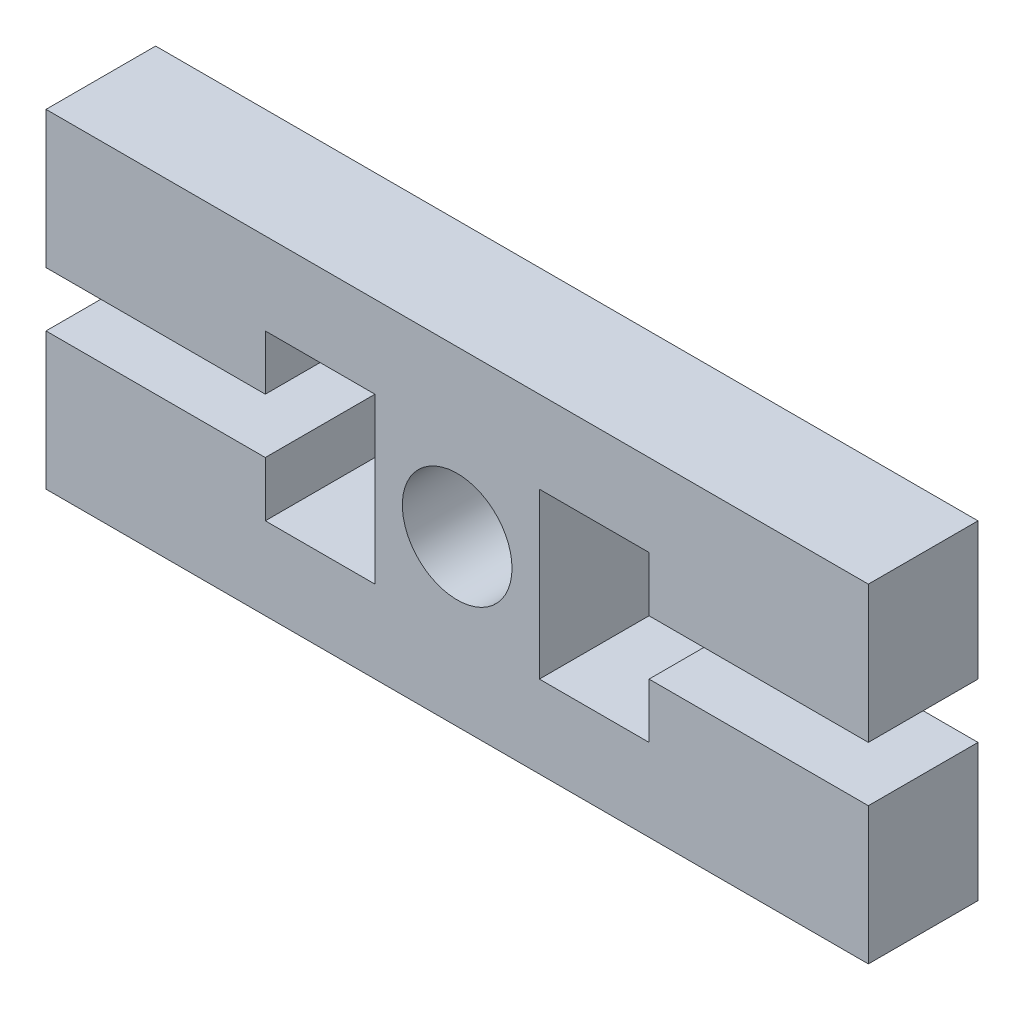
SolidWorks part; units mm, degrees
ref_plane "Front Plane" through (0, 0, 0) normal (0, 0, 1) x (1, 0, 0)
ref_plane "Top Plane" through (0, 0, 0) normal (0, 1, 0) x (1, 0, 0)
ref_plane "Right Plane" through (0, 0, 0) normal (1, 0, 0) x (0, 0, -1)
sketch "Sketch1" plane through (0, 0, 0) normal (0, 0, 1) x (1, 0, 0)
  line L0 (-44.45, 0) -> (-44.45, -6.35) construction
  line L1 (-95.25, 38.1) -> (95.25, 38.1)
  line L2 (-95.25, 38.1) -> (-95.25, 6.35)
  line L3 (-95.25, -38.1) -> (95.25, -38.1)
  line L4 (95.25, 38.1) -> (95.25, 6.35)
  line L5 (-95.25, 38.1) -> (95.25, -38.1) construction
  line L6 (-95.25, -38.1) -> (95.25, 38.1) construction
  line L7 (-19.05, 0) -> (0, 0) construction
  line L8 (-19.05, 0) -> (-19.05, 11.5629) construction
  line L9 (-19.05, 11.5629) -> (-19.05, 19.05) construction
  line L10 (-19.05, 19.05) -> (-44.45, 19.05) construction
  line L11 (-44.45, 19.05) -> (-44.45, 6.35) construction
  line L12 (-44.45, 6.35) -> (-44.45, 0) construction
  line L13 (-44.45, 6.35) -> (-95.25, 6.35) construction
  line L14 (0, 38.1) -> (0, 0) construction
  line L15 (0, 0) -> (0, -38.1) construction
  line L16 (-95.25, 6.35) -> (-44.45, 6.35)
  line L17 (-44.45, 6.35) -> (-44.45, 19.05)
  line L18 (-44.45, 19.05) -> (-19.05, 19.05)
  line L19 (-19.05, 19.05) -> (-19.05, -19.05)
  line L20 (19.05, 19.05) -> (19.05, -19.05)
  line L21 (44.45, 19.05) -> (19.05, 19.05)
  line L22 (44.45, 6.35) -> (44.45, 19.05)
  line L23 (95.25, 6.35) -> (44.45, 6.35)
  line L24 (95.25, -6.35) -> (44.45, -6.35)
  line L25 (44.45, -6.35) -> (44.45, -19.05)
  line L26 (44.45, -19.05) -> (19.05, -19.05)
  line L27 (-44.45, -19.05) -> (-19.05, -19.05)
  line L28 (-44.45, -6.35) -> (-44.45, -19.05)
  line L29 (-95.25, -6.35) -> (-44.45, -6.35)
  line L30 (-19.05, 0) -> (-44.45, 0) construction
  line L31 (0, 0) -> (19.05, 0) construction
  line L32 (-95.25, -6.35) -> (-95.25, -38.1)
  line L33 (95.25, -6.35) -> (95.25, -38.1)
  circle A0 centre (0, 0) radius 12.7
  point P0 (0, 0)
  point P9 (0, 0)
  point P28 (19.05, 0)
  point P32 (0, 0)
  dimension "D5" = 25.4
  dimension "D1" = 6.35
  dimension "D2" = 12.7
  dimension "D3" = 25.4
  dimension "D4" = 50.8
  dimension "D6" = 19.05
  dimension "D7" = 76.2
extrude "Boss-Extrude1" add sketch "Sketch1" along normal blind 25.4
